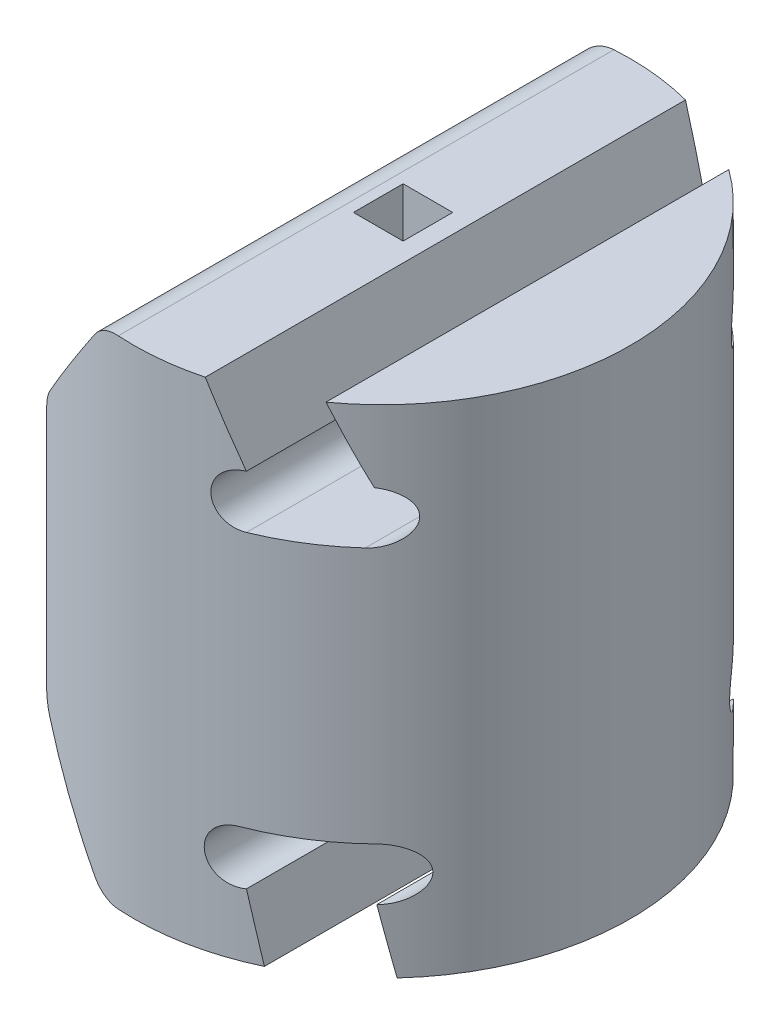
SolidWorks part; units mm, degrees
ref_plane "Front Plane" through (0, 0, 0) normal (0, 0, 1) x (1, 0, 0)
ref_plane "Top Plane" through (0, 0, 0) normal (0, 1, 0) x (1, 0, 0)
ref_plane "Right Plane" through (0, 0, 0) normal (1, 0, 0) x (0, 0, -1)
sketch "Sketch1" plane through (0, 0, 0) normal (0, 0, 1) x (1, 0, 0)
  line L0 (0, 12.0804) -> (0, -2.9196)
  line L1 (0, -2.9196) -> (-7.5, -2.9196)
  line L2 (-7.5, -2.9196) -> (-7.5, 12.0804)
  line L3 (-7.5, 12.0804) -> (0, 12.0804)
  dimension "D1" = 7.5
  dimension "D2" = 7.5
  dimension "D3" = 15
revolve "Revolve1" add sketch "Sketch1" angle 360 about L0
sketch "Sketch2" plane through (0, -2.9196, 0) normal (0, -1, 0) x (1, 0, 0)
  line L0 (-3.5, 6.6332) -> (-3.5, -6.6332)
  arc A0 (-3.5, 6.6332) -> (-3.5, -6.6332) centre (0, 0) ccw
  circle A1 centre (0, 0) radius 7.5 construction
  dimension "D1" = 3.5
  dimension "D2" = 3.5
extrude "Cut-Extrude1" cut sketch "Sketch2" against normal blind 20
sketch "Sketch4" plane through (0, -2.9196, 0) normal (0, -1, 0) x (1, 0, 0)
  line L3 (-0.162, 0.706) -> (1.338, 0.706)
  line L4 (-0.162, 0.706) -> (-0.162, -0.794)
  line L5 (-0.162, -0.794) -> (1.338, -0.794)
  line L6 (1.338, 0.706) -> (1.338, -0.794)
  dimension "D1" = 1.5
  dimension "D2" = 1.5
extrude "Cut-Extrude2" cut sketch "Sketch4" against normal blind 20
sketch "Sketch6" plane through (0, 0, 0) normal (0, 0, 1) x (1, 0, 0)
  line L2 (2.6844, 0.5898) -> (5.2213, 0.5898)
  line L6 (5.2213, -0.9945) -> (5.5242, -2.9196)
  line L7 (2.842, 8.3285) -> (5.042, 8.3285)
  line L11 (-3.5, -2.9196) -> (7.5, -2.9196) construction
  line L14 (5.1832, 9.9111) -> (4.3858, 12.0804)
  line L15 (7.5, 12.0804) -> (-3.5, 12.0804) construction
  line L16 (2.8401, 9.9285) -> (1.9093, 12.0804)
  line L17 (1.9093, 12.0804) -> (4.3858, 12.0804)
  line L21 (5.5242, -2.9196) -> (3.2179, -2.9196)
  line L28 (3.2179, -2.9196) -> (2.842, -0.9945)
  arc A0 (2.842, -0.9945) -> (2.6678, -1.01) centre (2.6844, -0.2102) cw
  arc A1 (2.6678, -1.01) -> (2.6844, 0.5898) centre (2.6844, -0.2102) cw
  arc A4 (2.8401, 9.9285) -> (2.2465, 9.6628) centre (2.842, 9.1285) ccw
  arc A5 (2.2465, 9.6628) -> (2.842, 8.3285) centre (2.842, 9.1285) ccw
  arc A6 (5.042, 8.3285) -> (5.6633, 9.6263) centre (5.042, 9.1261) ccw
  arc A7 (5.6633, 9.6263) -> (5.1832, 9.9111) centre (5.042, 9.1261) ccw
  arc A8 (5.2213, 0.5898) -> (5.2213, -0.9945) centre (5.2213, -0.2023) cw
  dimension "D3" = 0.8
  dimension "D4" = 0.8
  dimension "D9" = 0.8
  dimension "D10" = 0.8
  dimension "D12" = 0.7976
  dimension "D13" = 0.7976
  dimension "D7" = 2.4765
  dimension "D11" = 2.2
extrude "Cut-Extrude3" cut sketch "Sketch6" against normal through all both and the other way through all
sketch "Sketch7" plane through (0, 0, 0) normal (0, 0, 1) x (1, 0, 0)
  line L0 (-3.5, 0.6004) -> (-3.5, -2.9196)
  line L1 (-3.5, -2.9196) -> (-3.5, 12.0804) construction
  line L6 (1.9093, 12.0804) -> (-3.5, 12.0804) construction
  line L7 (-3.5, 12.0804) -> (-3.5, 8.5804)
  line L9 (-3.5, 12.0804) -> (-1, 12.0804)
  line L10 (-3.5, -2.9196) -> (-1, -2.9196)
  line L11 (-3.5, -2.9196) -> (3.2179, -2.9196) construction
  line L12 (-1, 12.0804) -> (-3.5, 8.5804)
  line L13 (-3.5, 0.6004) -> (-1, -2.9196)
  dimension "D1" = 3.5
  dimension "D2" = 3.52
  dimension "D3" = 2.5
  dimension "D4" = 2.5
extrude "Cut-Extrude4" cut sketch "Sketch7" against normal through all both and the other way through all
sketch "Sketch8" plane through (-3.5, 0, 0) normal (-1, 0, 0) x (0, 0, 1)
  line L1 (-6.2235, 8.1712) -> (6.1571, 8.1712)
  line L2 (-6.2235, 8.1712) -> (-6.2235, 0.9953)
  line L3 (-6.2235, 0.9953) -> (6.1571, 0.9953)
  line L4 (6.1571, 8.1712) -> (6.1571, 0.9953)
extrude "Cut-Extrude5" cut sketch "Sketch8" against normal blind 0.5
fillet "Fillet2" radius 1 4 edges at (-1, 12.0804, 0) (-3.5, 8.5804, 0) (-1, -2.9196, 0) (-3.5, 0.6004, 0)
fillet "Fillet5" radius 0.5 2 edges at (-3.5, 4.5832, 6.1571) (-3.5, 4.5832, -6.2235)
equation "\"mm\"=3.04027"
